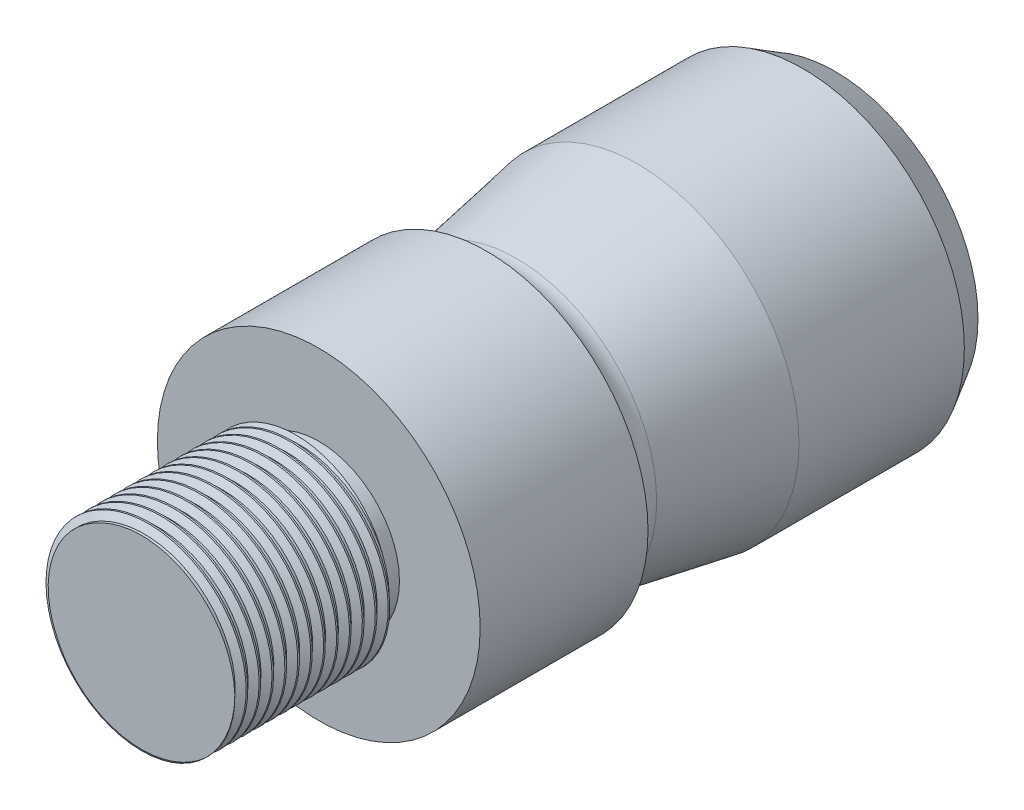
SolidWorks part; units mm, degrees
ref_plane "Front Plane" through (0, 0, 0) normal (0, 0, 1) x (1, 0, 0)
ref_plane "Top Plane" through (0, 0, 0) normal (0, 1, 0) x (1, 0, 0)
ref_plane "Right Plane" through (0, 0, 0) normal (1, 0, 0) x (0, 0, -1)
sketch "Sketch3" plane through (0, 0, 0) normal (0, 1, 0) x (1, 0, 0)
  line L0 (40.7796, 3.477) -> (40.7796, 111.477) construction
  line L1 (40.7796, 111.477) -> (62.8928, 111.477)
  line L2 (62.8928, 111.477) -> (65.7796, 106.477)
  line L3 (65.7796, 106.477) -> (65.7796, 80.8674)
  line L4 (65.7796, 80.8674) -> (62.4742, 62.1215)
  line L5 (65.7188, 57.4877) -> (65.7796, 57.477)
  line L6 (65.7796, 57.477) -> (65.7796, 31.477)
  line L7 (65.7796, 31.477) -> (53.2796, 31.477)
  line L8 (53.2796, 31.477) -> (53.2796, 28.477)
  line L9 (53.2796, 28.477) -> (55.7796, 28.477)
  line L10 (55.7796, 28.477) -> (55.7796, 3.477)
  line L11 (55.7796, 3.477) -> (40.7796, 3.477)
  line L12 (40.7796, 111.477) -> (40.7796, 3.477)
  arc A0 (62.4742, 62.1215) -> (65.7188, 57.4877) centre (66.4134, 61.4269) ccw
  point P13 (61.7796, 58.1823)
  dimension "D14" = 4
  dimension "D1" = 25
  dimension "D2" = 3
  dimension "D3" = 26
  dimension "D4" = 5
  dimension "D5" = 50
  dimension "D6" = 50
  dimension "D7" = 25
  dimension "D8" = 30
  dimension "D9" = 42
  dimension "D10" = 10
  dimension "D11" = 108
  dimension "D12" = 30
  dimension "D13" = 90
revolve "Revolve1" add sketch "Sketch3" angle 360 about L0
cosmetic thread "Cosmetic Thread1"
thread "Thread1" pitch 2 method cut profile "Thread Profile1" start angle 0, offset 5, length 31, pitch 2, diameter 30
ref_plane "Plane1" through (25.7796, 0, 1.523) normal (0, -1, 0) x (-1, 0, 0)
sketch "Thread Profile1" plane through (25.7796, 0, 1.523) normal (0, -1, 0) x (-1, 0, 0)
  line L0 (0, 0) -> (0, 2) construction
  line L11 (0, 0) -> (0, 1.75)
  line L12 (0, 1.75) -> (-1.0825, 1.125)
  line L13 (-1.0825, 1.125) -> (-1.0825, 0.625)
  line L15 (-1.0825, 0.625) -> (0, 0)
  line L17 (-1.0825, 0.875) -> (0, 0.875) construction
  point P2 (0, 0)
  dimension "Pitch" = 2
  dimension "Profile_Angle" = 60
  dimension "Profile_Land" = 0.5
  dimension "Profile_Height" = 1.0825
